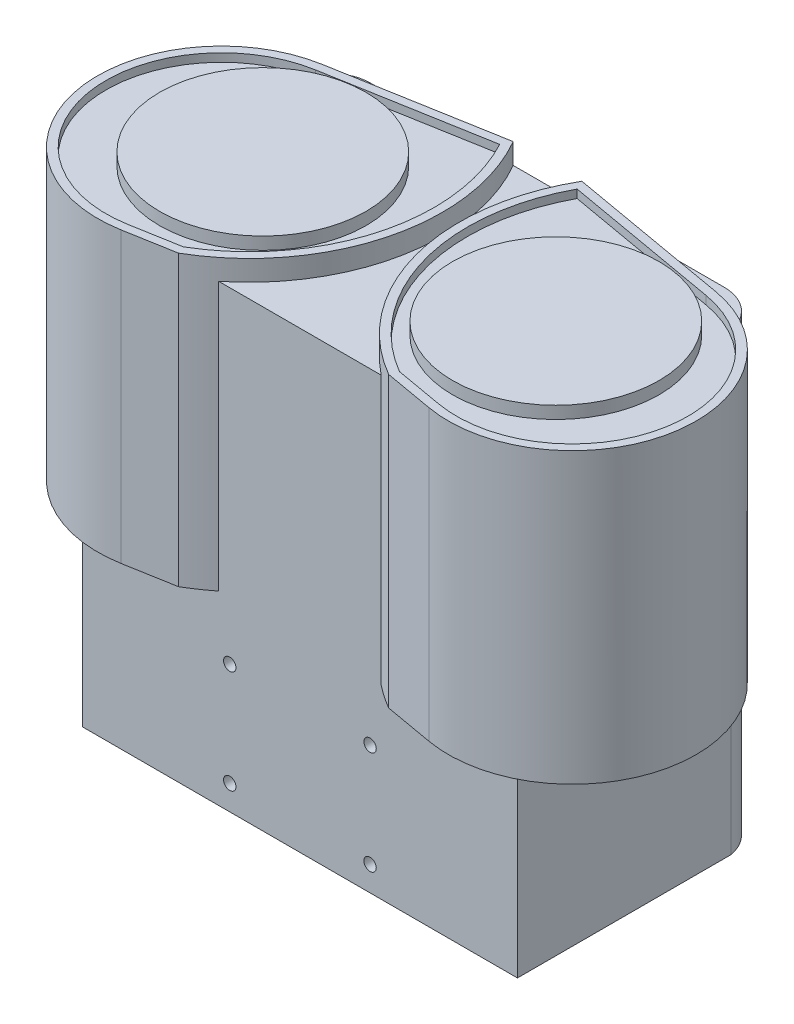
SolidWorks part; units mm, degrees
ref_plane "Alzado" through (0, 0, 0) normal (0, 0, 1) x (1, 0, 0)
ref_plane "Planta" through (0, 0, 0) normal (0, 1, 0) x (1, 0, 0)
ref_plane "Vista lateral" through (0, 0, 0) normal (1, 0, 0) x (0, 0, -1)
sketch "Croquis1" plane through (0, 0, 0) normal (0, 1, 0) x (1, 0, 0)
  line L4 (-5.2094, 29.5442) -> (34.1829, 36.4902)
  line L5 (5.2094, -29.5442) -> (17.0271, -27.4605)
  line L6 (-5.2094, 29.5442) -> (35.0476, 29.5442) construction
  line L7 (90.2094, 29.5442) -> (50.8171, 36.4902)
  line L8 (79.7906, -29.5442) -> (67.9729, -27.4605)
  arc A6 (-5.2094, 29.5442) -> (5.2094, -29.5442) centre (0, 0) ccw
  arc A8 (79.7906, -29.5442) -> (90.2094, 29.5442) centre (85, 0) ccw
  arc A15 (50.8171, 36.4902) -> (67.9729, -27.4605) centre (91.3703, 13.0927) ccw
  arc A16 (34.1829, 36.4902) -> (17.0271, -27.4605) centre (-6.3703, 13.0927) cw
  dimension "D1" = 40
  dimension "D2" = 12
  dimension "D4" = 10
  dimension "D6" = 12
  dimension "D7" = 30
  dimension "D5" = 60
  dimension "D8" = 40
  dimension "D10" = 85
  dimension "D11" = 10
extrude "Saliente-Extruir1" add sketch "Croquis1" along normal blind 60 and the other way blind 10
ref_plane "Plano1" through (0, 0, -36.4902) normal (0, 0, -1) x (-1, 0, 0)
sketch "Croquis5" plane through (0, 0, -36.4902) normal (0, 0, -1) x (-1, 0, 0)
  line L0 (-5.2094, -10) -> (30, -10) construction
  line L1 (-95.2106, 55) -> (10.2094, 55)
  line L2 (-95.2106, 55) -> (-95.2106, -10)
  line L3 (-95.2106, -10) -> (10.2094, -10)
  line L4 (10.2094, 55) -> (10.2094, -10)
  line L5 (5.2094, -10) -> (5.2094, 60) construction
  line L6 (30, 60) -> (-5.2094, 60) construction
  dimension "D1" = 5
  dimension "D2" = 5
  dimension "D3" = 105.42
extrude "Saliente-Extruir4" add sketch "Croquis5" against normal blind 60
fillet "Redondeo1" radius 10 2 edges at (-10.2094, 22.5, -36.4902) (95.2106, 22.5, -36.4902)
sketch "Croquis7" plane through (0, 60, 0) normal (0, 1, 0) x (1, 0, 0)
  line L4 (4.8621, -27.5746) -> (16.3289, -25.5527)
  line L5 (33.1279, 34.2733) -> (-4.8621, 27.5746)
  line L6 (4.8621, -27.5746) -> (16.3289, -25.5527)
  line L7 (33.1279, 34.2733) -> (-4.8621, 27.5746)
  line L10 (89.8621, 27.5746) -> (51.8721, 34.2733)
  line L11 (68.6711, -25.5527) -> (80.1379, -27.5746)
  line L12 (89.8621, 27.5746) -> (51.8721, 34.2733)
  line L13 (68.6711, -25.5527) -> (80.1379, -27.5746)
  arc A2 (16.3289, -25.5527) -> (33.1279, 34.2733) centre (-6.3703, 13.0927) ccw
  arc A4 (-4.8621, 27.5746) -> (4.8621, -27.5746) centre (0, 0) ccw
  arc A6 (-4.8621, 27.5746) -> (4.8621, -27.5746) centre (0, 0) ccw
  arc A8 (51.8721, 34.2733) -> (68.6711, -25.5527) centre (91.3703, 13.0927) ccw
  arc A10 (80.1379, -27.5746) -> (89.8621, 27.5746) centre (85, 0) ccw
  arc A12 (80.1379, -27.5746) -> (89.8621, 27.5746) centre (85, 0) ccw
  arc A13 (51.8721, 34.2733) -> (68.6711, -25.5527) centre (91.3703, 13.0927) ccw
  arc A14 (16.3289, -25.5527) -> (33.1279, 34.2733) centre (-6.3703, 13.0927) ccw
  dimension "D1" = 2
  dimension "D2" = 2
extrude "Cortar-Extruir3" cut sketch "Croquis7" against normal blind 2
sketch "Croquis8" plane through (0, 58, 0) normal (0, 1, 0) x (1, 0, 0)
  circle A0 centre (7, 3) radius 25
  circle A1 centre (85, 0) radius 13 construction
  circle A2 centre (78, 3) radius 25
  dimension "D1" = 7
  dimension "D3" = 7
  dimension "D5" = 50
  dimension "D2" = 3
  dimension "D4" = 3
extrude "Saliente-Extruir5" add sketch "Croquis8" along normal blind 3
sketch "Croquis9" plane through (0, -10, 0) normal (0, -1, 0) x (1, 0, 0)
  line L0 (95.2106, -28.2089) -> (95.2106, 23.5098)
  line L1 (62.1769, 23.5098) -> (22.8231, 23.5098)
  line L2 (22.8231, 23.5098) -> (-10.2094, 23.5098)
  line L3 (-10.2094, 23.5098) -> (-10.2094, -28.2093)
  line L4 (85.3594, -36.4902) -> (-0.3583, -36.4902)
  line L5 (62.1769, 23.5098) -> (95.2106, 23.5098)
  arc A1 (-10.2094, -28.2093) -> (-0.3583, -36.4902) centre (-0.3583, -26.4902) ccw
  arc A2 (-10.2094, -28.2093) -> (-0.3583, -36.4902) centre (-0.3583, -26.4902) ccw
  arc A3 (85.3594, -36.4902) -> (95.2106, -28.2089) centre (85.3594, -26.4902) ccw
extrude "Saliente-Extruir6" add sketch "Croquis9" along normal blind 45
sketch "Croquis10" plane through (0, 0, 23.5098) normal (0, 0, 1) x (1, 0, 0)
  line L1 (22.8231, 55) -> (62.1769, 55) construction
  line L2 (-10.2094, -10) -> (22.8231, -10) construction
  circle A0 centre (59.5006, -24) radius 1.5
  circle A1 centre (59.5006, -49) radius 1.5
  circle A2 centre (25.5006, -24) radius 1.5
  circle A3 centre (25.5006, -49) radius 1.5
  point P10 (42.5, 55)
  dimension "D1" = 34
  dimension "D2" = 25
  dimension "D3" = 3
  dimension "D4" = 16.9994
  dimension "D5" = 14
extrude "Cortar-Extruir4" cut sketch "Croquis10" against normal blind 5
sketch "Croquis11" plane through (0, 0, -36.4902) normal (0, 0, -1) x (-1, 0, 0)
  line L2 (-90.2094, 55) -> (-50.8171, 55) construction
  line L3 (0.3583, -55) -> (-85.3594, -55) construction
  circle A0 centre (-62.5005, 40) radius 1.5
  circle A1 centre (-22.5005, 40) radius 1.5
  circle A2 centre (-14.5005, -30) radius 1.5
  circle A3 centre (-70.5005, -30) radius 1.5
  point P15 (-42.5005, -55)
  dimension "D1" = 3
  dimension "D7" = 15
  dimension "D2" = 56
  dimension "D6" = 28
  dimension "D5" = 8
  dimension "D3" = 8
  dimension "D4" = 70
extrude "Cortar-Extruir5" cut sketch "Croquis11" against normal blind 5
